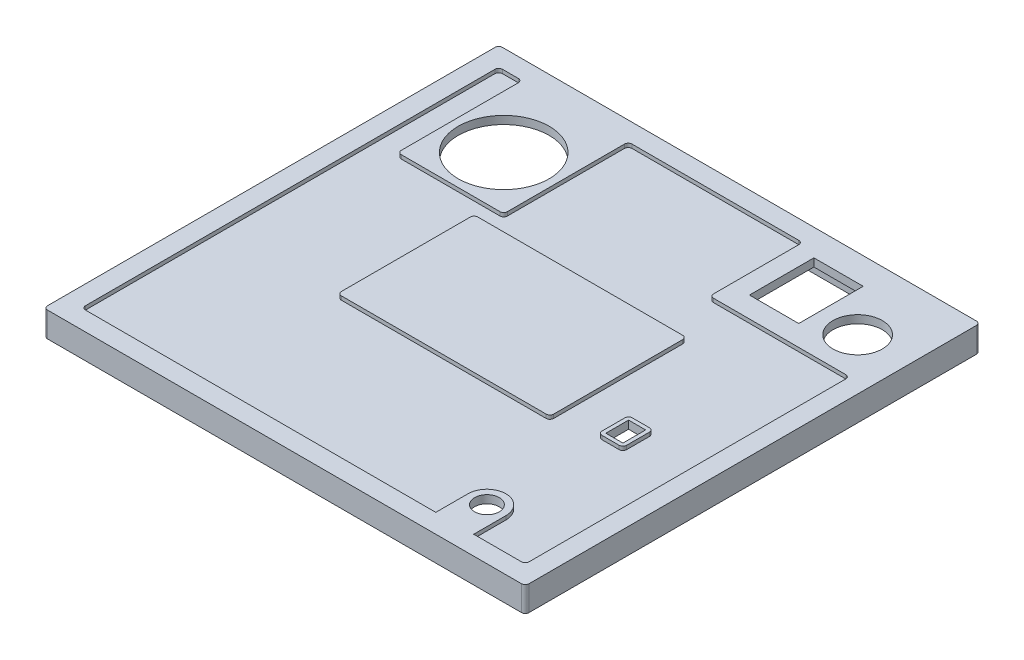
SolidWorks part; units mm, degrees
ref_plane "Alzado" through (0, 0, 0) normal (0, 0, 1) x (1, 0, 0)
ref_plane "Planta" through (0, 0, 0) normal (0, 1, 0) x (1, 0, 0)
ref_plane "Vista lateral" through (0, 0, 0) normal (1, 0, 0) x (0, 0, -1)
sketch "Croquis1" plane through (0, 0, 0) normal (0, 1, 0) x (1, 0, 0)
  line L1 (-48.8608, 29.4686) -> (78.1392, 29.4686)
  line L2 (-48.8608, 29.4686) -> (-48.8608, -90.5314)
  line L3 (-48.8608, -90.5314) -> (78.1392, -90.5314)
  line L4 (78.1392, 29.4686) -> (78.1392, -90.5314)
  dimension "D1" = 127
  dimension "D2" = 120
extrude "Saliente-Extruir1" add sketch "Croquis1" along normal blind 4.6
sketch "Croquis2" plane through (0, 0, 0) normal (0, -1, 0) x (1, 0, 0)
  line L0 (-48.8608, -29.4686) -> (-48.8608, 90.5314) construction
  line L1 (-42.8608, 84.5314) -> (72.1392, 84.5314)
  line L2 (-42.8608, 84.5314) -> (-42.8608, -23.4686)
  line L3 (-42.8608, -23.4686) -> (72.1392, -23.4686)
  line L4 (72.1392, 84.5314) -> (72.1392, -23.4686)
  line L5 (78.1392, 90.5314) -> (78.1392, -29.4686) construction
  line L6 (-48.8608, 90.5314) -> (78.1392, 90.5314) construction
  line L7 (78.1392, -29.4686) -> (-48.8608, -29.4686) construction
  dimension "D1" = 6
  dimension "D2" = 6
  dimension "D3" = 6
  dimension "D4" = 6
extrude "Cortar-Extruir1" cut sketch "Croquis2" against normal blind 2.5
sketch "Croquis4" plane through (0, 2.5, 0) normal (0, -1, 0) x (1, 0, 0)
  line L0 (-48.8608, 90.5314) -> (78.1392, 90.5314) construction
  line L1 (78.1392, 90.5314) -> (78.1392, -29.4686) construction
  circle A0 centre (54.5392, 77.0414) radius 3.25
  dimension "D1" = 6.5
  dimension "D2" = 13.49
  dimension "D3" = 23.6
extrude "Cortar-Extruir2" cut sketch "Croquis4" against normal blind 5
sketch "Croquis5" plane through (0, 2.5, 0) normal (0, -1, 0) x (1, 0, 0)
  line L0 (78.1392, 90.5314) -> (78.1392, -29.4686) construction
  line L3 (78.1392, -29.4686) -> (-48.8608, -29.4686) construction
  circle A0 centre (64.6092, -10.6686) radius 6.5
  dimension "D1" = 13
  dimension "D2" = 13.53
  dimension "D3" = 18.8
extrude "Cortar-Extruir3" cut sketch "Croquis5" against normal blind 5
sketch "Croquis9" plane through (0, 2.5, 0) normal (0, -1, 0) x (-1, 0, 0)
  line L1 (-41.2692, 5.4686) -> (-54.2692, 5.4686)
  line L2 (-41.2692, 5.4686) -> (-41.2692, 22.4686)
  line L3 (-41.2692, 22.4686) -> (-54.2692, 22.4686)
  line L4 (-54.2692, 5.4686) -> (-54.2692, 22.4686)
  line L5 (-78.1392, 29.4686) -> (48.8608, 29.4686) construction
  line L6 (-78.1392, -90.5314) -> (-78.1392, 29.4686) construction
  dimension "D1" = 13
  dimension "D2" = 17
  dimension "D3" = 23.87
  dimension "D4" = 7
extrude "Cortar-Extruir5" cut sketch "Croquis9" against normal blind 5
sketch "Croquis10" plane through (0, 4.6, 0) normal (0, 1, 0) x (1, 0, 0)
  line L0 (-43.8608, 24.4686) -> (36.2692, 24.4686)
  line L1 (36.2692, 24.4686) -> (36.2692, 0)
  line L2 (36.2692, 0) -> (73.1392, 0)
  line L3 (73.1392, 0) -> (73.1392, -73.0414)
  line L5 (49.5392, -72.0414) -> (49.5392, -85.5314)
  line L6 (49.5392, -85.5314) -> (-43.8608, -85.5314)
  line L7 (-43.8608, -85.5314) -> (-43.8608, 24.4686)
  line L8 (-48.8608, 29.4686) -> (-48.8608, -90.5314) construction
  line L9 (78.1392, 29.4686) -> (-48.8608, 29.4686) construction
  line L10 (41.2692, 22.4686) -> (41.2692, 5.4686) construction
  line L12 (78.1392, -90.5314) -> (78.1392, 29.4686) construction
  line L18 (49.5392, -72.0414) -> (59.5392, -72.0414)
  line L19 (59.5392, -72.0414) -> (59.5392, -85.5314)
  line L21 (73.1392, -85.5314) -> (73.1392, -73.0414)
  line L22 (59.5392, -85.5314) -> (73.1392, -85.5314)
  circle A2 centre (54.5392, -77.0414) radius 3.25 construction
  dimension "D1" = 5
  dimension "D2" = 5
  dimension "D3" = 5
  dimension "D4" = 5
  dimension "D5" = 5
  dimension "D6" = 5
  dimension "D8" = 5
extrude "Cortar-Extruir7" cut sketch "Croquis10" against normal blind 1
sketch "Croquis12" plane through (0, 3.6, 0) normal (0, 1, 0) x (1, 0, 0)
  line L0 (78.1392, 29.4686) -> (-48.8608, 29.4686) construction
  line L1 (-48.8608, 29.4686) -> (-48.8608, -90.5314) construction
  circle A0 centre (-23.7008, 5.6186) radius 12
  dimension "D1" = 24
  dimension "D2" = 23.85
  dimension "D3" = 25.16
extrude "Cortar-Extruir8" cut sketch "Croquis12" against normal blind 10 and the other way blind 10
sketch "Croquis14" plane through (0, 3.6, 0) normal (0, 1, 0) x (1, 0, 0)
  line L0 (-37.7008, 24.4686) -> (-37.7008, -8.3814)
  line L1 (36.2692, 24.4686) -> (-43.8608, 24.4686) construction
  line L2 (-37.7008, -8.3814) -> (-9.7008, -8.3814)
  line L3 (-9.7008, -8.3814) -> (-9.7008, 24.4686)
  line L4 (-9.7008, 24.4686) -> (-37.7008, 24.4686)
  circle A0 centre (-23.7008, 5.6186) radius 12 construction
  circle M4 centre (-23.7008, 5.6186) radius 12
  dimension "D1" = 14
  dimension "D2" = 14
  dimension "D3" = 14
extrude "Saliente-Extruir3" add sketch "Croquis14" along normal blind 1 contours M4 | L4 L0 L2 L3 region at (-23.7008, 3.6, -5.6186)
sketch "Croquis11" plane through (0, 3.6, 0) normal (0, 1, 0) x (1, 0, 0)
  line L0 (14.6392, 29.4686) -> (14.6392, -90.5314) construction
  line L1 (78.1392, 29.4686) -> (-48.8608, 29.4686) construction
  line L2 (-48.8608, -90.5314) -> (78.1392, -90.5314) construction
  line L3 (-48.8608, -30.5314) -> (78.1392, -30.5314) construction
  line L4 (-48.8608, 29.4686) -> (-48.8608, -90.5314) construction
  line L5 (78.1392, -90.5314) -> (78.1392, 29.4686) construction
  line L7 (-13.3608, -12.5314) -> (42.6392, -12.5314)
  line L8 (-13.3608, -12.5314) -> (-13.3608, -48.5314)
  line L9 (-13.3608, -48.5314) -> (42.6392, -48.5314)
  line L10 (42.6392, -12.5314) -> (42.6392, -48.5314)
  dimension "D1" = 56
  dimension "D2" = 36
  dimension "D3" = 18
  dimension "D4" = 28
fillet "Redondeo4" 2 edges at (49.5392, 4.1, 72.0414) (59.5392, 4.1, 72.0414) type full round first side face at (49.5392, 4.1, 78.7864) second side face at (59.5392, 4.1, 78.7864) middle face at (54.5392, 4.1, 72.0414)
extrude "Saliente-Extruir2" add sketch "Croquis11" along normal blind 1
fillet "Redondeo6" radius 1 10 edges at (42.6392, 4.1, 48.5314) (42.6392, 4.1, 12.5314) (-13.3608, 4.1, 12.5314) (-13.3608, 4.1, 48.5314) (-43.8608, 4.1, 85.5314) (73.1392, 4.1, 85.5314) (-43.8608, 4.1, -24.4686) (36.2692, 4.1, -24.4686) (73.1392, 4.1, 0) (36.2692, 4.1, 0)
fillet "Redondeo7" radius 1 4 edges at (-9.7008, 4.1, -24.4686) (-9.7008, 4.1, 8.3814) (-37.7008, 4.1, 8.3814) (-37.7008, 4.1, -24.4686)
sketch "Croquis15" plane through (0, 0, 0) normal (0, -1, 0) x (-1, 0, 0)
  line L0 (47.3608, -89.0314) -> (-76.6392, -89.0314)
  line L1 (-76.6392, -89.0314) -> (-76.6392, 27.9686)
  line L2 (-76.6392, 27.9686) -> (47.3608, 27.9686)
  line L3 (47.3608, 27.9686) -> (47.3608, -89.0314)
  line L4 (48.8608, -90.5314) -> (-78.1392, -90.5314) construction
  line L5 (-78.1392, -90.5314) -> (-78.1392, 29.4686) construction
  line L6 (48.8608, 29.4686) -> (48.8608, -90.5314) construction
  line L7 (-78.1392, 29.4686) -> (48.8608, 29.4686) construction
  line M9 (48.8608, -90.5314) -> (48.8608, 29.4686)
  line M10 (48.8608, 29.4686) -> (-78.1392, 29.4686)
  line M11 (-78.1392, 29.4686) -> (-78.1392, -90.5314)
  line M12 (-78.1392, -90.5314) -> (48.8608, -90.5314)
  dimension "D1" = 1.5
  dimension "D2" = 1.5
  dimension "D3" = 1.5
  dimension "D4" = 1.5
extrude "Saliente-Extruir4" add sketch "Croquis15" along normal blind 2 contours L2 L3 L0 L1 M12 M9 M10 M11 region at (14.6392, 0, 90.3567)
sketch "Croquis16" plane through (0, 3.6, 0) normal (0, 1, 0) x (1, 0, 0)
  line L0 (-48.8608, -90.5314) -> (78.1392, -90.5314) construction
  line L1 (53.8892, -39.0314) -> (58.3892, -39.0314)
  line L2 (53.8892, -39.0314) -> (53.8892, -45.0314)
  line L3 (53.8892, -45.0314) -> (58.3892, -45.0314)
  line L4 (58.3892, -39.0314) -> (58.3892, -45.0314)
  line L5 (78.1392, -90.5314) -> (78.1392, 29.4686) construction
  dimension "D1" = 6
  dimension "D2" = 4.5
  dimension "D3" = 45.5
  dimension "D4" = 19.75
extrude "Cortar-Extruir9" cut sketch "Croquis16" against normal blind 20
sketch "Croquis18" plane through (0, 3.6, 0) normal (0, 1, 0) x (1, 0, 0)
  line L0 (58.3892, -39.0314) -> (53.8892, -39.0314) construction
  line L1 (52.8892, -38.0314) -> (59.3892, -38.0314)
  line L2 (52.8892, -38.0314) -> (52.8892, -46.0314)
  line L3 (52.8892, -46.0314) -> (59.3892, -46.0314)
  line L4 (59.3892, -38.0314) -> (59.3892, -46.0314)
  line L5 (58.3892, -45.0314) -> (58.3892, -39.0314) construction
  line L6 (53.8892, -45.0314) -> (58.3892, -45.0314) construction
  line L7 (53.8892, -39.0314) -> (53.8892, -45.0314) construction
  line M5 (58.3892, -45.0314) -> (53.8892, -45.0314)
  line M6 (53.8892, -45.0314) -> (53.8892, -39.0314)
  line M7 (53.8892, -39.0314) -> (58.3892, -39.0314)
  line M8 (58.3892, -39.0314) -> (58.3892, -45.0314)
  dimension "D1" = 1
  dimension "D2" = 1
  dimension "D3" = 1
  dimension "D4" = 1
extrude "Saliente-Extruir5" add sketch "Croquis18" along normal blind 1 contours L4 L1 L2 L3 M8 M5 M6 M7 region at (56.1392, 3.6, 38.1345)
fillet "Redondeo8" radius 1 4 edges at (59.3892, 4.1, 38.0314) (52.8892, 4.1, 38.0314) (52.8892, 4.1, 46.0314) (59.3892, 4.1, 46.0314)
fillet "Redondeo9" radius 1 4 edges at (-48.8608, 1.3, 90.5314) (-48.8608, 1.3, -29.4686) (78.1392, 1.3, -29.4686) (78.1392, 1.3, 90.5314)
sketch "Croquis19" plane through (0, 4.6, 0) normal (0, 1, 0) x (1, 0, 0)
  line L0 (105.3333, 146.5) -> (526.6667, 146.5) construction
